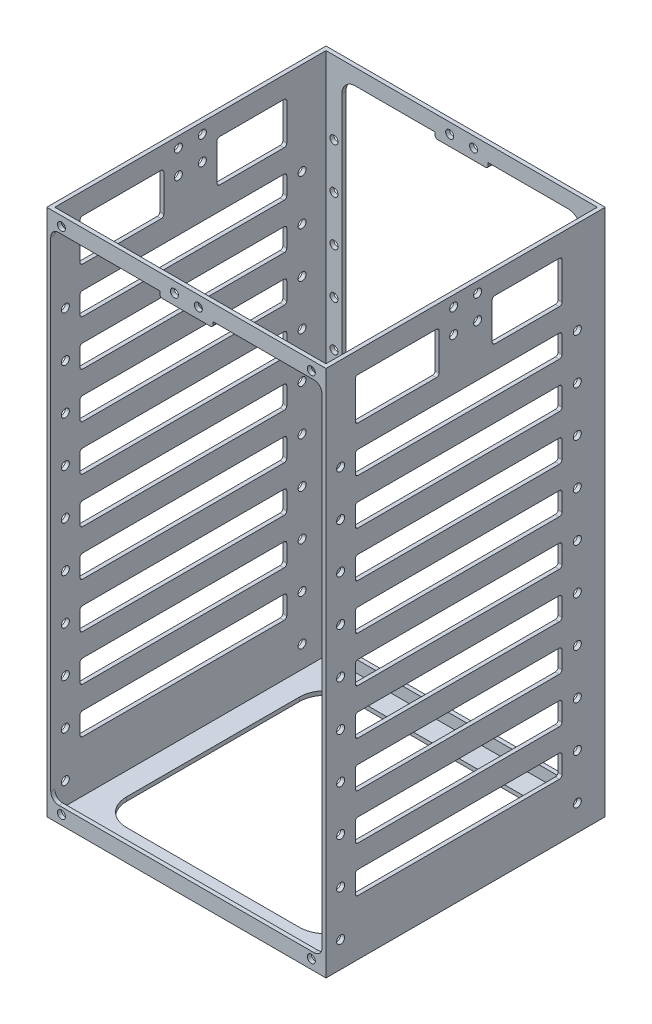
SolidWorks part; units mm, degrees
ref_plane "Front Plane" through (0, 0, 0) normal (0, 0, 1) x (1, 0, 0)
ref_plane "Top Plane" through (0, 0, 0) normal (0, 1, 0) x (1, 0, 0)
ref_plane "Right Plane" through (0, 0, 0) normal (1, 0, 0) x (0, 0, -1)
sketch "Sketch1" plane through (0, 0, 0) normal (0, 1, 0) x (1, 0, 0)
  line L1 (-52.5, -52.5) -> (52.5, -52.5)
  line L2 (-52.5, -52.5) -> (-52.5, 52.5)
  line L3 (-52.5, 52.5) -> (52.5, 52.5)
  line L4 (52.5, -52.5) -> (52.5, 52.5)
  line L5 (-52.5, -52.5) -> (52.5, 52.5) construction
  line L6 (-52.5, 52.5) -> (52.5, -52.5) construction
  line L7 (-32.5, -42.5) -> (32.5, -42.5)
  line L8 (-42.5, -32.5) -> (-42.5, 32.5)
  line L9 (-32.5, 42.5) -> (32.5, 42.5)
  line L10 (42.5, -32.5) -> (42.5, 32.5)
  line L11 (-42.5, -42.5) -> (42.5, 42.5) construction
  line L12 (-42.5, 42.5) -> (42.5, -42.5) construction
  arc A0 (32.5, -42.5) -> (42.5, -32.5) centre (32.5, -32.5) ccw
  arc A1 (32.5, 42.5) -> (42.5, 32.5) centre (32.5, 32.5) cw
  arc A2 (-42.5, 32.5) -> (-32.5, 42.5) centre (-32.5, 32.5) cw
  arc A3 (-32.5, -42.5) -> (-42.5, -32.5) centre (-32.5, -32.5) cw
  point P0 (0, 0)
  point P6 (0, 0)
  dimension "D3" = 10
  dimension "D1" = 105
  dimension "D2" = 42.5
extrude "Boss-Extrude2" add sketch "Sketch1" along normal blind 1.5 contours A3 L7 A0 L10 A1 L9 A2 L8 | L2 L1 L4 L3 region at (0, 0, 0)
sketch "Sketch3" plane through (0, 1.5, 0) normal (0, 1, 0) x (1, 0, 0)
  line L1 (-52.5, -52.5) -> (52.5, -52.5)
  line L2 (-52.5, -52.5) -> (-52.5, 52.5)
  line L3 (-52.5, 52.5) -> (52.5, 52.5)
  line L4 (52.5, -52.5) -> (52.5, 52.5)
  line L5 (-52.5, -52.5) -> (52.5, 52.5) construction
  line L6 (-52.5, 52.5) -> (52.5, -52.5) construction
  line L7 (-51, -51) -> (51, -51)
  line L8 (-51, -51) -> (-51, 51)
  line L9 (-51, 51) -> (51, 51)
  line L10 (51, -51) -> (51, 51)
  line L11 (-51, -51) -> (51, 51) construction
  line L12 (-51, 51) -> (51, -51) construction
  point P0 (0, 0)
  point P7 (0, 0)
  dimension "D1" = 1.5
extrude "Boss-Extrude3" add sketch "Sketch3" along normal blind 197 contours L8 L7 L10 L9 | L2 L3 L4 L1
sketch "Sketch4" plane through (0, 0, -52.5) normal (0, 0, 1) x (1, 0, 0)
  line L0 (-52.5, 0) -> (52.5, 0) construction
  line L1 (-40, 6) -> (40, 6)
  line L2 (-45, 11) -> (-45, 187.5)
  line L3 (-40, 192.5) -> (40, 192.5)
  line L4 (45, 11) -> (45, 187.5)
  line L5 (-45, 6) -> (45, 192.5) construction
  line L6 (-45, 192.5) -> (45, 6) construction
  line L7 (52.5, 198.5) -> (52.5, 0) construction
  line L8 (-51, 198.5) -> (51, 198.5) construction
  line L9 (-52.5, 198.5) -> (-52.5, 0) construction
  arc A0 (-40, 6) -> (-45, 11) centre (-40, 11) cw
  arc A1 (40, 6) -> (45, 11) centre (40, 11) ccw
  arc A2 (40, 192.5) -> (45, 187.5) centre (40, 187.5) cw
  arc A3 (-45, 187.5) -> (-40, 192.5) centre (-40, 187.5) cw
  point P0 (0, 99.25)
  dimension "D5" = 5
  dimension "D1" = 6
  dimension "D2" = 7.5
  dimension "D3" = 6
  dimension "D4" = 7.5
extrude "Cut-Extrude1" cut sketch "Sketch4" along normal up to surface (1.5 mm away) up to face at (0, 100, -51)
sketch "Sketch5" plane through (0, 0, 52.5) normal (0, 0, 1) x (1, 0, 0)
  line L0 (-52.5, 198.5) -> (52.5, 198.5) construction
  line L1 (-48, 6) -> (48, 6)
  line L2 (-51, 9) -> (-51, 189.5)
  line L3 (-48, 192.5) -> (48, 192.5)
  line L4 (51, 9) -> (51, 189.5)
  line L5 (-51, 6) -> (51, 192.5) construction
  line L6 (-51, 192.5) -> (51, 6) construction
  line L7 (-52.5, 1.5) -> (52.5, 1.5) construction
  line L8 (-52.5, 198.5) -> (-52.5, 0) construction
  line L9 (52.5, 198.5) -> (52.5, 0) construction
  arc A0 (48, 6) -> (51, 9) centre (48, 9) ccw
  arc A1 (-48, 6) -> (-51, 9) centre (-48, 9) cw
  arc A2 (48, 192.5) -> (51, 189.5) centre (48, 189.5) cw
  arc A3 (-51, 189.5) -> (-48, 192.5) centre (-48, 189.5) cw
  point P0 (0, 99.25)
  dimension "D5" = 3
  dimension "D1" = 6
  dimension "D2" = 4.5
  dimension "D3" = 1.5
  dimension "D4" = 1.5
sketch "Sketch6" plane through (52.5, 0, 0) normal (1, 0, 0) x (0, 0, -1)
  line L0 (-52.5, 6) -> (-52.5, 192.5) construction
  line L2 (-52.5, 0) -> (52.5, 0) construction
  circle A0 centre (-47, 9.75) radius 1.5
  circle A1 centre (42, 9.75) radius 1.5
  circle A2 centre (-47, 26.85) radius 1.5
  circle A3 centre (42, 26.85) radius 1.5
  circle A4 centre (-47, 43.95) radius 1.5
  circle A5 centre (42, 43.95) radius 1.5
  circle A6 centre (-47, 61.05) radius 1.5
  circle A7 centre (42, 61.05) radius 1.5
  circle A8 centre (-47, 78.15) radius 1.5
  circle A9 centre (42, 78.15) radius 1.5
  circle A10 centre (-47, 95.25) radius 1.5
  circle A11 centre (42, 95.25) radius 1.5
  circle A12 centre (-47, 112.35) radius 1.5
  circle A13 centre (42, 112.35) radius 1.5
  circle A14 centre (-47, 129.45) radius 1.5
  circle A15 centre (42, 129.45) radius 1.5
  circle A16 centre (-47, 146.55) radius 1.5
  circle A17 centre (42, 146.55) radius 1.5
  circle A18 centre (-47, 163.65) radius 1.5
  circle A19 centre (42, 163.65) radius 1.5
  dimension "D4" = 3
  dimension "D5" = 3
  dimension "D1" = 5.5
  dimension "D2" = 89
  dimension "D3" = 9.75
  dimension "D7" = 17.1
  dimension "D9" = 17.1
  dimension "D6" = 9
  dimension "D8" = 2
extrude "Cut-Extrude2" cut sketch "Sketch6" against normal through all
extrude "Cut-Extrude3" cut sketch "Sketch5" against normal up to surface (1.5 mm away) up to face at (0, 100, 51)
sketch "Sketch7" plane through (52.5, 0, 0) normal (1, 0, 0) x (0, 0, -1)
  line L0 (-41.5, 38.95) -> (-41.5, 45.45)
  line L1 (-40.5, 20.85) -> (35.25, 20.85)
  line L2 (-41.5, 21.85) -> (-41.5, 28.35)
  line L3 (-40.5, 29.35) -> (35.25, 29.35)
  line L4 (36.25, 21.85) -> (36.25, 28.35)
  line L5 (-41.5, 20.85) -> (36.25, 29.35) construction
  line L6 (-41.5, 29.35) -> (36.25, 20.85) construction
  line L7 (-41.5, 158.65) -> (-41.5, 165.15)
  line L8 (-40.5, 37.95) -> (35.25, 37.95)
  line L9 (36.25, 38.95) -> (36.25, 45.45)
  line L10 (-40.5, 46.45) -> (35.25, 46.45)
  line L11 (-41.5, 56.05) -> (-41.5, 62.55)
  line L12 (-40.5, 55.05) -> (35.25, 55.05)
  line L13 (36.25, 56.05) -> (36.25, 62.55)
  line L14 (-40.5, 63.55) -> (35.25, 63.55)
  line L15 (-41.5, 73.15) -> (-41.5, 79.65)
  line L16 (-40.5, 72.15) -> (35.25, 72.15)
  line L17 (36.25, 73.15) -> (36.25, 79.65)
  line L18 (-40.5, 80.65) -> (35.25, 80.65)
  line L19 (-41.5, 90.25) -> (-41.5, 96.75)
  line L20 (-40.5, 89.25) -> (35.25, 89.25)
  line L21 (36.25, 90.25) -> (36.25, 96.75)
  line L22 (-40.5, 97.75) -> (35.25, 97.75)
  line L23 (-41.5, 107.35) -> (-41.5, 113.85)
  line L24 (-40.5, 106.35) -> (35.25, 106.35)
  line L25 (36.25, 107.35) -> (36.25, 113.85)
  line L26 (-40.5, 114.85) -> (35.25, 114.85)
  line L27 (-41.5, 124.45) -> (-41.5, 130.95)
  line L28 (-40.5, 123.45) -> (35.25, 123.45)
  line L29 (36.25, 124.45) -> (36.25, 130.95)
  line L30 (-40.5, 131.95) -> (35.25, 131.95)
  line L31 (-41.5, 141.55) -> (-41.5, 148.05)
  line L32 (-40.5, 140.55) -> (35.25, 140.55)
  line L33 (36.25, 141.55) -> (36.25, 148.05)
  line L34 (-40.5, 149.05) -> (35.25, 149.05)
  line L35 (-40.5, 157.65) -> (35.25, 157.65)
  line L36 (36.25, 158.65) -> (36.25, 165.15)
  line L37 (-40.5, 166.15) -> (35.25, 166.15)
  line L38 (-41.5, 141.55) -> (-41.5, 158.65) construction
  circle A0 centre (-47, 9.75) radius 1.5 construction
  arc A1 (35.25, 29.35) -> (36.25, 28.35) centre (35.25, 28.35) cw
  arc A2 (35.25, 20.85) -> (36.25, 21.85) centre (35.25, 21.85) ccw
  arc A3 (-40.5, 20.85) -> (-41.5, 21.85) centre (-40.5, 21.85) cw
  arc A4 (-41.5, 28.35) -> (-40.5, 29.35) centre (-40.5, 28.35) cw
  arc A5 (-41.5, 45.45) -> (-40.5, 46.45) centre (-40.5, 45.45) cw
  arc A6 (-40.5, 37.95) -> (-41.5, 38.95) centre (-40.5, 38.95) cw
  arc A7 (35.25, 37.95) -> (36.25, 38.95) centre (35.25, 38.95) ccw
  arc A8 (35.25, 46.45) -> (36.25, 45.45) centre (35.25, 45.45) cw
  arc A9 (-41.5, 62.55) -> (-40.5, 63.55) centre (-40.5, 62.55) cw
  arc A10 (-40.5, 55.05) -> (-41.5, 56.05) centre (-40.5, 56.05) cw
  arc A11 (35.25, 55.05) -> (36.25, 56.05) centre (35.25, 56.05) ccw
  arc A12 (35.25, 63.55) -> (36.25, 62.55) centre (35.25, 62.55) cw
  arc A13 (-41.5, 79.65) -> (-40.5, 80.65) centre (-40.5, 79.65) cw
  arc A14 (-40.5, 72.15) -> (-41.5, 73.15) centre (-40.5, 73.15) cw
  arc A15 (35.25, 72.15) -> (36.25, 73.15) centre (35.25, 73.15) ccw
  arc A16 (35.25, 80.65) -> (36.25, 79.65) centre (35.25, 79.65) cw
  arc A17 (-41.5, 96.75) -> (-40.5, 97.75) centre (-40.5, 96.75) cw
  arc A18 (-40.5, 89.25) -> (-41.5, 90.25) centre (-40.5, 90.25) cw
  arc A19 (35.25, 89.25) -> (36.25, 90.25) centre (35.25, 90.25) ccw
  arc A20 (35.25, 97.75) -> (36.25, 96.75) centre (35.25, 96.75) cw
  arc A21 (-41.5, 113.85) -> (-40.5, 114.85) centre (-40.5, 113.85) cw
  arc A22 (-40.5, 106.35) -> (-41.5, 107.35) centre (-40.5, 107.35) cw
  arc A23 (35.25, 106.35) -> (36.25, 107.35) centre (35.25, 107.35) ccw
  arc A24 (35.25, 114.85) -> (36.25, 113.85) centre (35.25, 113.85) cw
  arc A25 (-41.5, 130.95) -> (-40.5, 131.95) centre (-40.5, 130.95) cw
  arc A26 (-40.5, 123.45) -> (-41.5, 124.45) centre (-40.5, 124.45) cw
  arc A27 (35.25, 123.45) -> (36.25, 124.45) centre (35.25, 124.45) ccw
  arc A28 (35.25, 131.95) -> (36.25, 130.95) centre (35.25, 130.95) cw
  arc A29 (-41.5, 148.05) -> (-40.5, 149.05) centre (-40.5, 148.05) cw
  arc A30 (-40.5, 140.55) -> (-41.5, 141.55) centre (-40.5, 141.55) cw
  arc A31 (35.25, 140.55) -> (36.25, 141.55) centre (35.25, 141.55) ccw
  arc A32 (35.25, 149.05) -> (36.25, 148.05) centre (35.25, 148.05) cw
  arc A33 (-41.5, 165.15) -> (-40.5, 166.15) centre (-40.5, 165.15) cw
  arc A34 (-40.5, 157.65) -> (-41.5, 158.65) centre (-40.5, 158.65) cw
  circle A35 centre (42, 9.75) radius 1.5 construction
  arc A36 (35.25, 157.65) -> (36.25, 158.65) centre (35.25, 158.65) ccw
  arc A37 (35.25, 166.15) -> (36.25, 165.15) centre (35.25, 165.15) cw
  point P0 (-2.625, 25.1)
  dimension "D5" = 1
  dimension "D3" = 5.75
  dimension "D1" = 8.5
  dimension "D2" = 11.1
  dimension "D4" = 5.5
  dimension "D7" = 8.6
  dimension "D9" = 8.6
  dimension "D6" = 8
  dimension "D8" = 2
extrude "Cut-Extrude4" cut sketch "Sketch7" against normal through all
sketch "Sketch8" plane through (52.5, 0, 0) normal (1, 0, 0) x (0, 0, -1)
  line L7 (-52.5, 198.5) -> (52.5, 198.5) construction
  line L15 (-40.5, 190.5) -> (35.25, 190.5)
  line L16 (-41.5, 189.5) -> (-41.5, 175.75)
  line L17 (-40.5, 174.75) -> (35.25, 174.75)
  line L18 (36.25, 189.5) -> (36.25, 175.75)
  line L19 (35.25, 166.15) -> (-40.5, 166.15) construction
  arc A15 (35.25, 190.5) -> (36.25, 189.5) centre (35.25, 189.5) cw
  arc A16 (35.25, 174.75) -> (36.25, 175.75) centre (35.25, 175.75) ccw
  arc A17 (-41.5, 175.75) -> (-40.5, 174.75) centre (-40.5, 175.75) ccw
  arc A18 (-40.5, 190.5) -> (-41.5, 189.5) centre (-40.5, 189.5) ccw
  circle A19 centre (-47, 163.65) radius 1.5 construction
  circle A20 centre (42, 163.65) radius 1.5 construction
  point P0 (-2.625, 162.85)
  dimension "D6" = 1
  dimension "D2" = 8.6
  dimension "D8" = 8
  dimension "D9" = 5.5
  dimension "D10" = 5.75
extrude "Cut-Extrude5" cut sketch "Sketch8" against normal through all
sketch "Sketch15" plane through (52.5, 0, 0) normal (1, 0, 0) x (0, 0, -1)
  line L7 (35.25, 190.5) -> (-40.5, 190.5) construction
  line L8 (-10, 190.5) -> (10, 190.5)
  line L9 (-10, 190.5) -> (-10, 174.75)
  line L10 (-10, 174.75) -> (10, 174.75)
  line L11 (10, 190.5) -> (10, 174.75)
  line L12 (-40.5, 174.75) -> (35.25, 174.75) construction
  line L13 (-52.5, 198.5) -> (-52.5, 0) construction
  dimension "D1" = 20
  dimension "D2" = 42.5
extrude "Boss-Extrude4" add sketch "Sketch15" against normal up to surface (1.5 mm away) up to face at (51, 182.625, 2.625)
sketch "Sketch16" plane through (-52.5, 0, 0) normal (-1, 0, 0) x (0, 0, 1)
  line L7 (-10, 190.5) -> (10, 190.5)
  line L8 (-10, 190.5) -> (-10, 174.75)
  line L9 (-10, 174.75) -> (10, 174.75)
  line L10 (10, 190.5) -> (10, 174.75)
extrude "Boss-Extrude5" add sketch "Sketch16" against normal up to surface (1.5 mm away) up to face at (-51, 182.625, 2.625)
sketch "Sketch9" plane through (52.5, 0, 0) normal (1, 0, 0) x (0, 0, -1)
  line L0 (-52.5, 198.5) -> (52.5, 198.5) construction
  line L1 (-52.5, 198.5) -> (-52.5, 0) construction
  line L2 (-10.0428, 190) -> (10.2919, 190) construction
  circle A0 centre (-4.5, 194.5) radius 1.5
  circle A1 centre (4.5, 194.5) radius 1.5
  circle A2 centre (4.5, 185.5) radius 1.5
  circle A3 centre (-4.5, 185.5) radius 1.5
  dimension "D1" = 3
  dimension "D3" = 9
  dimension "D5" = 3
  dimension "D2" = 4
  dimension "D4" = 48
  dimension "D6" = 4.5
extrude "Cut-Extrude6" cut sketch "Sketch9" against normal through all
fillet "Fillet1" radius 1 8 edges at (-51.75, 174.75, 10) (-51.75, 190.5, 10) (-51.75, 190.5, -10) (-51.75, 174.75, -10) (51.75, 190.5, 10) (51.75, 174.75, 10) (51.75, 174.75, -10) (51.75, 190.5, -10)
sketch "Sketch18" plane through (0, 0, -52.5) normal (0, 0, -1) x (-1, 0, 0)
  line L0 (-40, 192.5) -> (40, 192.5) construction
  line L1 (-10, 192.5) -> (10, 192.5)
  line L2 (-10, 192.5) -> (-10, 191.5)
  line L3 (-9, 190.5) -> (9, 190.5)
  line L4 (10, 192.5) -> (10, 191.5)
  line L5 (-52.5, 198.5) -> (-52.5, 0) construction
  arc A0 (9, 190.5) -> (10, 191.5) centre (9, 191.5) ccw
  arc A1 (-10, 191.5) -> (-9, 190.5) centre (-9, 191.5) ccw
  dimension "D3" = 1
  dimension "D1" = 2
  dimension "D2" = 20
  dimension "D4" = 42.5
extrude "Boss-Extrude7" add sketch "Sketch18" against normal up to surface (1.5 mm away) up to face at (0, 99.25, -51)
sketch "Sketch17" plane through (0, 0, 52.5) normal (0, 0, 1) x (1, 0, 0)
  line L0 (48, 192.5) -> (-48, 192.5) construction
  line L1 (-10, 192.5) -> (10, 192.5)
  line L2 (-10, 192.5) -> (-10, 191.5)
  line L3 (-9, 190.5) -> (9, 190.5)
  line L4 (10, 192.5) -> (10, 191.5)
  line L5 (-52.5, 198.5) -> (-52.5, 0) construction
  arc A0 (9, 190.5) -> (10, 191.5) centre (9, 191.5) ccw
  arc A1 (-10, 191.5) -> (-9, 190.5) centre (-9, 191.5) ccw
  dimension "D4" = 1
  dimension "D1" = 20
  dimension "D2" = 42.5
  dimension "D3" = 2
extrude "Boss-Extrude6" add sketch "Sketch17" against normal up to surface (1.5 mm away) up to face at (0, 193.7071, 51)
sketch "Sketch19" plane through (0, 0, 52.5) normal (0, 0, 1) x (1, 0, 0)
  line L0 (0, 198.5) -> (0, 190.5) construction
  line L1 (-9, 190.5) -> (9, 190.5) construction
  line L3 (-52.5, 198.5) -> (52.5, 198.5) construction
  circle A0 centre (-4.5, 194.5) radius 1.5
  circle A1 centre (4.5, 194.5) radius 1.5
  dimension "D1" = 3
  dimension "D2" = 4
  dimension "D3" = 4.5
extrude "Cut-Extrude7" cut sketch "Sketch19" against normal through all
sketch "Sketch20" plane through (0, 0, 52.5) normal (0, 0, 1) x (1, 0, 0)
  line L0 (-52.5, 198.5) -> (-52.5, 0) construction
  line L1 (-52.5, 0) -> (52.5, 0) construction
  line L2 (0, 198.5) -> (0, 0) construction
  line L3 (-52.5, 198.5) -> (52.5, 198.5) construction
  circle A0 centre (-46.98, 3.5) radius 1.5
  circle A1 centre (-46.98, 195) radius 1.5
  circle A2 centre (46.98, 3.5) radius 1.5
  circle A3 centre (46.98, 195) radius 1.5
  dimension "D1" = 3
  dimension "D4" = 3
  dimension "D2" = 5.52
  dimension "D3" = 3.5
  dimension "D5" = 5.52
  dimension "D6" = 3.5
extrude "Cut-Extrude8" cut sketch "Sketch20" against normal up to surface (1.5 mm away) up to face at (-6, 194.5, 51)
sketch "Sketch23" plane through (0, 0, -52.5) normal (0, 0, -1) x (-1, 0, 0)
  line L0 (-52.5, 198.5) -> (-52.5, 0) construction
  line L1 (52.5, 0) -> (-52.5, 0) construction
  line L2 (0, 198.5) -> (0, 0) construction
  line L3 (52.5, 198.5) -> (-52.5, 198.5) construction
  circle A0 centre (-48, 17.05) radius 1.5
  circle A2 centre (-48, 34.15) radius 1.5
  circle A3 centre (-48, 51.25) radius 1.5
  circle A4 centre (-48, 68.35) radius 1.5
  circle A5 centre (-48, 85.45) radius 1.5
  circle A6 centre (-48, 102.55) radius 1.5
  circle A7 centre (-48, 119.65) radius 1.5
  circle A8 centre (-48, 136.75) radius 1.5
  circle A9 centre (-48, 153.85) radius 1.5
  circle A10 centre (-48, 170.95) radius 1.5
  circle A11 centre (48, 170.95) radius 1.5
  circle A12 centre (48, 153.85) radius 1.5
  circle A13 centre (48, 136.75) radius 1.5
  circle A14 centre (48, 119.65) radius 1.5
  circle A15 centre (48, 102.55) radius 1.5
  circle A16 centre (48, 85.45) radius 1.5
  circle A17 centre (48, 68.35) radius 1.5
  circle A18 centre (48, 51.25) radius 1.5
  circle A19 centre (48, 34.15) radius 1.5
  circle A20 centre (48, 17.05) radius 1.5
  dimension "D1" = 3
  dimension "D2" = 4.5
  dimension "D3" = 17.05
  dimension "D5" = 17.1
  dimension "D4" = 10
extrude "Cut-Extrude10" cut sketch "Sketch23" against normal up to surface (1.5 mm away) up to face at (-6, 194.5, -51)
